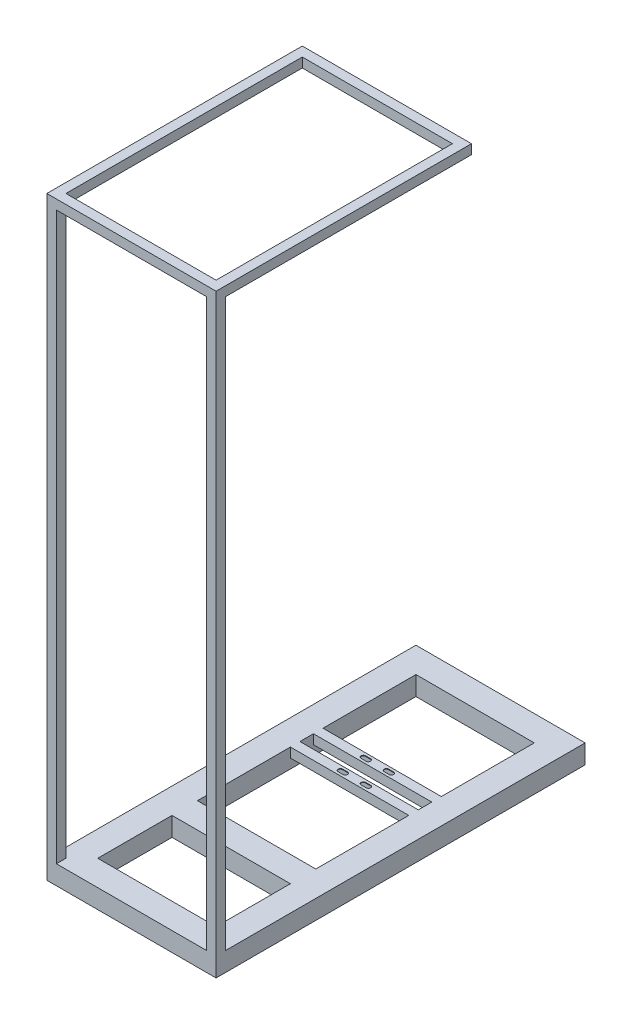
SolidWorks part; units mm, degrees
ref_plane "Front Plane" through (0, 0, 0) normal (0, 0, 1) x (1, 0, 0)
ref_plane "Top Plane" through (0, 0, 0) normal (0, 1, 0) x (1, 0, 0)
ref_plane "Right Plane" through (0, 0, 0) normal (1, 0, 0) x (0, 0, -1)
sketch "Sketch1" plane through (0, 0, 0) normal (0, 1, 0) x (1, 0, 0)
  line L1 (169, 269) -> (-169, 269)
  line L2 (169, 269) -> (169, -269)
  line L3 (169, -269) -> (-169, -269)
  line L4 (-169, 269) -> (-169, -269)
  line L5 (169, 269) -> (-169, -269) construction
  line L6 (169, -269) -> (-169, 269) construction
  point P0 (0, 0)
  dimension "D1" = 538
  dimension "D2" = 338
sketch "Sketch2" plane through (0, 0, 0) normal (0, 0, 1) x (1, 0, 0)
  line L5 (-119.4, 36.9) -> (-167.8, 36.9)
  line L6 (169, 0) -> (-169, 0) construction
  line L11 (-118.2, 38.1) -> (-169, 38.1)
  line L12 (-118.2, 38.1) -> (-118.2, 0)
  line L13 (-118.2, 0) -> (-169, 0)
  line L14 (-169, 38.1) -> (-169, 0)
  line L15 (-118.2, 38.1) -> (-169, 0) construction
  line L16 (-118.2, 0) -> (-169, 38.1) construction
  line L17 (169, 0) -> (-169, 0) construction
  line L18 (-119.4, 36.9) -> (-119.4, 1.2)
  line L19 (-119.4, 1.2) -> (-167.8, 1.2)
  line L20 (-167.8, 36.9) -> (-167.8, 1.2)
  line L21 (-119.4, 36.9) -> (-167.8, 1.2) construction
  line L22 (-119.4, 1.2) -> (-167.8, 36.9) construction
  point P0 (-143.6, 19.05)
  point P9 (-143.6, 19.05)
  dimension "D1" = 50.8
  dimension "D2" = 38.1
  dimension "D3" = 1.2
  dimension "D4" = 1.2
sweep "Sweep1" add profiles "Sketch2" path "Sketch1"
sketch "Sketch3" plane through (0, 38.1, 0) normal (0, 1, 0) x (1, 0, 0)
  line L0 (-118.2, -218.2) -> (-118.2, 218.2) construction
  line L1 (118.2, 13.5) -> (-118.2, 13.5)
  line L2 (118.2, 13.5) -> (118.2, -13.5)
  line L3 (118.2, -13.5) -> (-118.2, -13.5)
  line L4 (-118.2, 13.5) -> (-118.2, -13.5)
  line L5 (118.2, 13.5) -> (-118.2, -13.5) construction
  line L6 (118.2, -13.5) -> (-118.2, 13.5) construction
  line L7 (-32.5, 0) -> (0, 0) construction
  line L8 (-17.981, 22.981) -> (-27.981, 22.981) construction
  line L9 (-17.981, 18.481) -> (-27.981, 18.481)
  line L10 (-17.981, 27.481) -> (-27.981, 27.481)
  line L11 (17.981, 22.981) -> (27.981, 22.981) construction
  line L12 (0, 0) -> (-22.981, 22.981) construction
  line L13 (17.981, 27.481) -> (27.981, 27.481)
  line L14 (17.981, 18.481) -> (27.981, 18.481)
  line L15 (17.981, -22.981) -> (27.981, -22.981) construction
  line L16 (17.981, -18.481) -> (27.981, -18.481)
  line L17 (17.981, -27.481) -> (27.981, -27.481)
  line L18 (-17.981, -22.981) -> (-27.981, -22.981) construction
  line L19 (-17.981, -27.481) -> (-27.981, -27.481)
  line L20 (-17.981, -18.481) -> (-27.981, -18.481)
  circle A2 centre (0, 0) radius 32.5 construction
  arc A3 (17.981, 27.481) -> (17.981, 18.481) centre (17.981, 22.981) ccw
  arc A4 (27.981, 18.481) -> (27.981, 27.481) centre (27.981, 22.981) ccw
  arc A5 (17.981, -18.481) -> (17.981, -27.481) centre (17.981, -22.981) ccw
  arc A6 (27.981, -27.481) -> (27.981, -18.481) centre (27.981, -22.981) ccw
  arc A7 (-17.981, -27.481) -> (-17.981, -18.481) centre (-17.981, -22.981) ccw
  arc A8 (-27.981, -18.481) -> (-27.981, -27.481) centre (-27.981, -22.981) ccw
  arc A9 (-17.981, 18.481) -> (-17.981, 27.481) centre (-17.981, 22.981) ccw
  arc A10 (-27.981, 27.481) -> (-27.981, 18.481) centre (-27.981, 22.981) ccw
  point P1 (0, 0)
  point P13 (-22.981, 22.981)
  point P15 (-22.981, 22.981)
  point P17 (22.981, 22.981)
  point P18 (22.981, 22.981)
  point P21 (22.981, -22.981)
  point P22 (-22.981, -22.981)
  point P29 (0, 0)
  point P33 (22.981, -22.981)
  point P40 (-22.981, -22.981)
  dimension "D2" = 65
  dimension "D3" = 45
  dimension "D5" = 9
  dimension "D1" = 27
  dimension "D6" = 10
  dimension "D7" = 4
sketch "Sketch5" plane through (0, 0, 0) normal (0, 0, 1) x (1, 0, 0)
  line L1 (-118.2, 19.05) -> (-137.25, 19.05)
  line L2 (-118.2, 19.05) -> (-118.2, 38.1)
  line L3 (-118.2, 38.1) -> (-137.25, 38.1)
  line L4 (-137.25, 19.05) -> (-137.25, 38.1)
  line L5 (-118.2, 19.05) -> (-137.25, 38.1) construction
  line L6 (-118.2, 38.1) -> (-137.25, 19.05) construction
  line L8 (-119.4, 36.9) -> (-136.05, 36.9)
  line L9 (-119.4, 36.9) -> (-119.4, 20.25)
  line L10 (-119.4, 20.25) -> (-136.05, 20.25)
  line L11 (-136.05, 36.9) -> (-136.05, 20.25)
  line L12 (-119.4, 36.9) -> (-136.05, 20.25) construction
  line L13 (-119.4, 20.25) -> (-136.05, 36.9) construction
  line L14 (118.2, 38.1) -> (-118.2, 38.1) construction
  point P0 (-127.725, 28.575)
  point P5 (0, 0)
  point P7 (-118.2, 28.575)
  point P9 (-127.725, 28.575)
  point P14 (0, 0)
  point P20 (0, 0)
  point P21 (0, 0)
  dimension "D1" = 19.05
  dimension "D2" = 1.2
sweep "Sweep4" add profiles "Sketch5" path "Sketch3"
extrude "Cut-Extrude1" cut sketch "Sketch3<10>" against normal up to surface (19.05 mm away)
sketch "Sketch3<10>" plane through (0, 38.1, 0) normal (0, 1, 0) x (1, 0, 0) same geometry as "Sketch3"
sketch "Sketch12" plane through (0, 38.1, 0) normal (0, 1, 0) x (1, 0, 0)
  line L0 (118.2, -218.2) -> (-118.2, -218.2) construction
  line L1 (-169, -218.2) -> (169, -218.2)
  line L2 (-169, -218.2) -> (-169, -468.2)
  line L3 (-169, -468.2) -> (169, -468.2)
  line L4 (169, -218.2) -> (169, -468.2)
  line L5 (-169, -269) -> (-169, 269) construction
  line L6 (169, 269) -> (169, -269) construction
  point P5 (0, 0)
  point P7 (0, 0)
  point P8 (0, 0)
  dimension "D1" = 250
sketch "Sketch13" plane through (0, 0, 269) normal (0, 0, 1) x (1, 0, 0)
  line L1 (-167.8, 36.9) -> (-119.4, 36.9)
  line L2 (-167.8, 36.9) -> (-167.8, 1.2)
  line L3 (-167.8, 1.2) -> (-119.4, 1.2)
  line L4 (-119.4, 36.9) -> (-119.4, 1.2)
  line L5 (-167.8, 36.9) -> (-119.4, 1.2) construction
  line L6 (-167.8, 1.2) -> (-119.4, 36.9) construction
  line L7 (-169, 38.1) -> (-118.2, 38.1)
  line L8 (-169, 38.1) -> (-169, 0)
  line L9 (-169, 0) -> (-118.2, 0)
  line L10 (-118.2, 38.1) -> (-118.2, 0)
  line L11 (-169, 38.1) -> (-118.2, 0) construction
  line L12 (-169, 0) -> (-118.2, 38.1) construction
  point P0 (-143.6, 19.05)
  point P5 (-143.6, 19.05)
  point P10 (0, 0)
  point P11 (0, 0)
  point P12 (0, 0)
  point P16 (0, 0)
sweep "Sweep5" add profiles "Sketch13" path "Sketch12"
sketch "Sketch14" plane through (0, 0, 468.2) normal (0, 0, 1) x (1, 0, 0)
  line L1 (-169, 19.05) -> (169, 19.05)
  line L2 (-169, 19.05) -> (-169, 1188.1)
  line L3 (-169, 1188.1) -> (169, 1188.1)
  line L4 (169, 19.05) -> (169, 1188.1)
  line L5 (-169, 38.1) -> (-169, 0) construction
  line L6 (169, 38.1) -> (169, 0) construction
  point P4 (0, 0)
  point P5 (0, 0)
  point P6 (-169, 71.2184)
  point P9 (-169, 38.1)
  point P12 (0, 0)
  point P13 (0, 0)
  point P14 (0, 0)
  dimension "D1" = 19.05
  dimension "D2" = 1150
sketch "Sketch15" plane through (0, 38.1, 0) normal (0, 1, 0) x (1, 0, 0)
  line L1 (-149.95, -449.15) -> (-169, -449.15)
  line L2 (-149.95, -449.15) -> (-149.95, -468.2)
  line L3 (-149.95, -468.2) -> (-169, -468.2)
  line L4 (-169, -449.15) -> (-169, -468.2)
  line L5 (-149.95, -449.15) -> (-169, -468.2) construction
  line L6 (-149.95, -468.2) -> (-169, -449.15) construction
  line L7 (-151.15, -450.35) -> (-167.8, -450.35)
  line L8 (-151.15, -450.35) -> (-151.15, -467)
  line L9 (-151.15, -467) -> (-167.8, -467)
  line L10 (-167.8, -450.35) -> (-167.8, -467)
  line L11 (-151.15, -450.35) -> (-167.8, -467) construction
  line L12 (-151.15, -467) -> (-167.8, -450.35) construction
  point P0 (-159.475, -458.675)
  point P6 (-159.475, -458.675)
  dimension "D1" = 19.05
  dimension "D2" = 1.2
sweep "Sweep6" add profiles "Sketch15" path "Sketch14"
sketch "Sketch16" plane through (0, 1188.1, 0) normal (0, 1, 0) x (1, 0, 0)
  line L1 (169, -468.2) -> (-169, -468.2)
  line L2 (169, -468.2) -> (169, 42)
  line L3 (169, 42) -> (-169, 42)
  line L4 (-169, -468.2) -> (-169, 42)
  line L5 (-169, -7) -> (169, -7)
  dimension "D1" = 510.2
  dimension "D2" = 49
sketch "Sketch18" plane through (0, 0, 468.2) normal (0, 0, 1) x (1, 0, 0)
  line L1 (-149.95, 1169.05) -> (-169, 1169.05)
  line L2 (-149.95, 1169.05) -> (-149.95, 1188.1)
  line L3 (-149.95, 1188.1) -> (-169, 1188.1)
  line L4 (-169, 1169.05) -> (-169, 1188.1)
  line L5 (-149.95, 1169.05) -> (-169, 1188.1) construction
  line L6 (-149.95, 1188.1) -> (-169, 1169.05) construction
  line L7 (-151.15, 1186.9) -> (-167.8, 1186.9)
  line L8 (-151.15, 1186.9) -> (-151.15, 1170.25)
  line L9 (-151.15, 1170.25) -> (-167.8, 1170.25)
  line L10 (-167.8, 1186.9) -> (-167.8, 1170.25)
  line L11 (-151.15, 1186.9) -> (-167.8, 1170.25) construction
  line L12 (-151.15, 1170.25) -> (-167.8, 1186.9) construction
  point P0 (-159.475, 1178.575)
  point P9 (-159.475, 1178.575)
  dimension "D1" = 1.2
sweep "Sweep7" add profiles "Sketch18" path "Sketch16"
